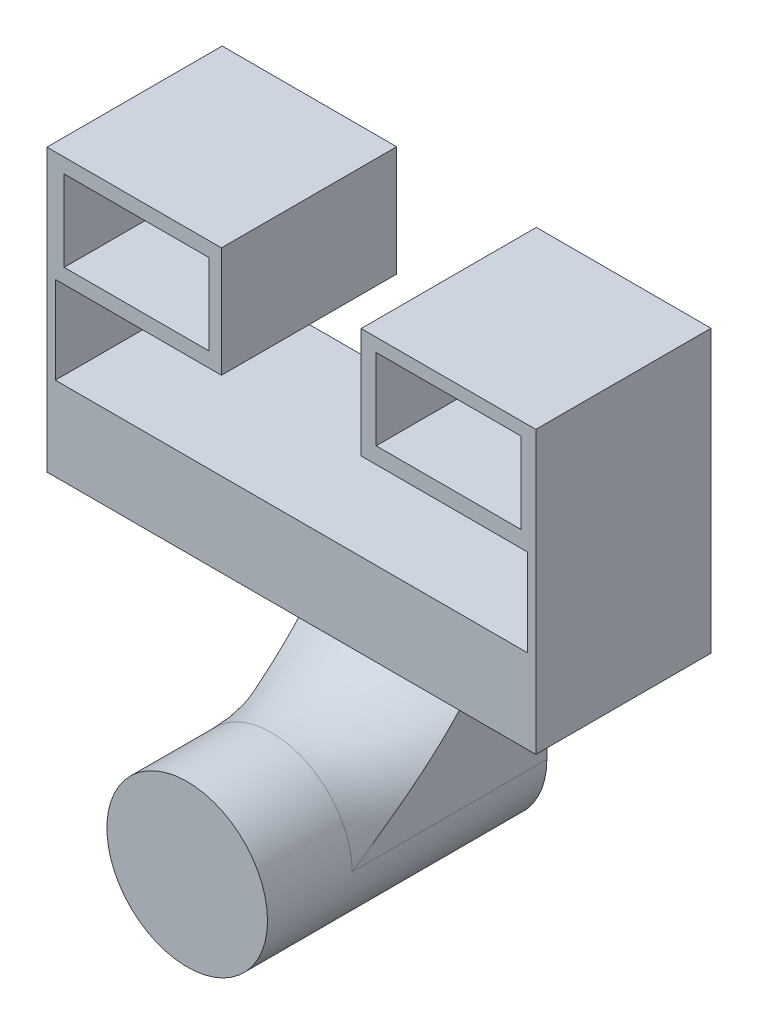
SolidWorks part; units mm, degrees
material "6061-T6 (SS)"
ref_plane "Front Plane" through (0, 0, 0) normal (0, 0, 1) x (1, 0, 0)
ref_plane "Top Plane" through (0, 0, 0) normal (0, 1, 0) x (1, 0, 0)
ref_plane "Right Plane" through (0, 0, 0) normal (1, 0, 0) x (0, 0, -1)
sketch "Sketch1" plane through (0, 0, 0) normal (0, 0, 1) x (1, 0, 0)
  circle A0 centre (0, 0) radius 14.605
extrude "Boss-Extrude1" add sketch "Sketch1" against normal blind 50.8 contours A0
sketch "Sketch2" plane through (0, 0, -50.8) normal (0, 0, -1) x (-1, 0, 0)
  line L1 (-14.605, 0) -> (14.605, 0)
  line L2 (-14.605, 0) -> (-14.605, 31.6499)
  line L3 (-14.605, 31.6499) -> (14.605, 31.6499)
  line L4 (14.605, 0) -> (14.605, 31.6499)
  circle A0 centre (0, 0) radius 14.605 construction
extrude "Boss-Extrude3" add sketch "Sketch2" against normal blind 4.2901
sketch "Sketch3" plane through (0, 31.6499, 0) normal (0, 1, 0) x (1, 0, 0)
  line L0 (-14.605, 50.8) -> (-44.4425, 50.8)
  line L1 (-44.4425, 50.8) -> (-44.4425, 18.942)
  line L2 (-44.4425, 18.942) -> (44.4575, 18.942)
  line L3 (44.4575, 18.942) -> (44.4575, 50.8)
  line L4 (44.4575, 50.8) -> (-14.605, 50.8)
extrude "Boss-Extrude4" add sketch "Sketch3" along normal blind 15.24
sketch "Sketch4" plane through (0, 46.8899, 0) normal (0, 1, 0) x (1, 0, 0)
  line L0 (44.4575, 50.8) -> (42.9335, 50.8)
  line L1 (44.4575, 50.8) -> (-44.4425, 50.8) construction
  line L2 (42.9335, 50.8) -> (42.9335, 18.942)
  line L3 (-44.4425, 18.942) -> (44.4575, 18.942) construction
  line L4 (42.9335, 18.942) -> (44.4575, 18.942)
  line L5 (44.4575, 18.942) -> (44.4575, 50.8)
  line L6 (-44.4425, 50.8) -> (-44.4425, 18.942)
  line L7 (-44.4425, 18.942) -> (-42.9185, 18.942)
  line L8 (-42.9185, 18.942) -> (-42.9185, 50.8)
  line L9 (-42.9185, 50.8) -> (-44.4425, 50.8)
extrude "Boss-Extrude6" add sketch "Sketch4" along normal blind 15.875
sketch "Sketch5" plane through (0, 62.7649, 0) normal (0, 1, 0) x (1, 0, 0)
  line L0 (-44.4425, 50.8) -> (-12.7159, 50.8)
  line L1 (42.9335, 50.8) -> (-42.9185, 50.8) construction
  line L2 (-12.7159, 50.8) -> (-12.7159, 18.942)
  line L3 (-42.9185, 18.942) -> (42.9335, 18.942) construction
  line L4 (-12.7159, 18.942) -> (-44.4425, 18.942)
  line L5 (-44.4425, 18.942) -> (-44.4425, 50.8)
  line L6 (44.4575, 50.8) -> (12.6898, 50.8)
  line L7 (12.6898, 50.8) -> (12.6898, 18.942)
  line L8 (12.6898, 18.942) -> (44.4575, 18.942)
  line L9 (44.4575, 18.942) -> (44.4575, 50.8)
extrude "Boss-Extrude7" add sketch "Sketch5" along normal blind 20.066
fillet "Fillet2" radius 31.115 1 edges at (0, 14.605, -46.5099)
sketch "Sketch6" plane through (0, 0, -18.942) normal (0, 0, 1) x (1, 0, 0)
  line L1 (-41.3137, 80.1692) -> (-14.9623, 80.1692)
  line L2 (-41.3137, 80.1692) -> (-41.3137, 65.4641)
  line L3 (-41.3137, 65.4641) -> (-14.9623, 65.4641)
  line L4 (-14.9623, 80.1692) -> (-14.9623, 65.4641)
  line L8 (15.4184, 80.428) -> (41.7698, 80.428)
  line L9 (15.4184, 80.428) -> (15.4184, 65.7229)
  line L10 (15.4184, 65.7229) -> (41.7698, 65.7229)
  line L11 (41.7698, 80.428) -> (41.7698, 65.7229)
  line L12 (-44.4425, 82.8309) -> (-12.7159, 82.8309) construction
extrude "Cut-Extrude1" cut sketch "Sketch6" against normal blind 58.42
fillet "Fillet9" radius 5.08 1 edges at (0, 31.6499, -43.147)
